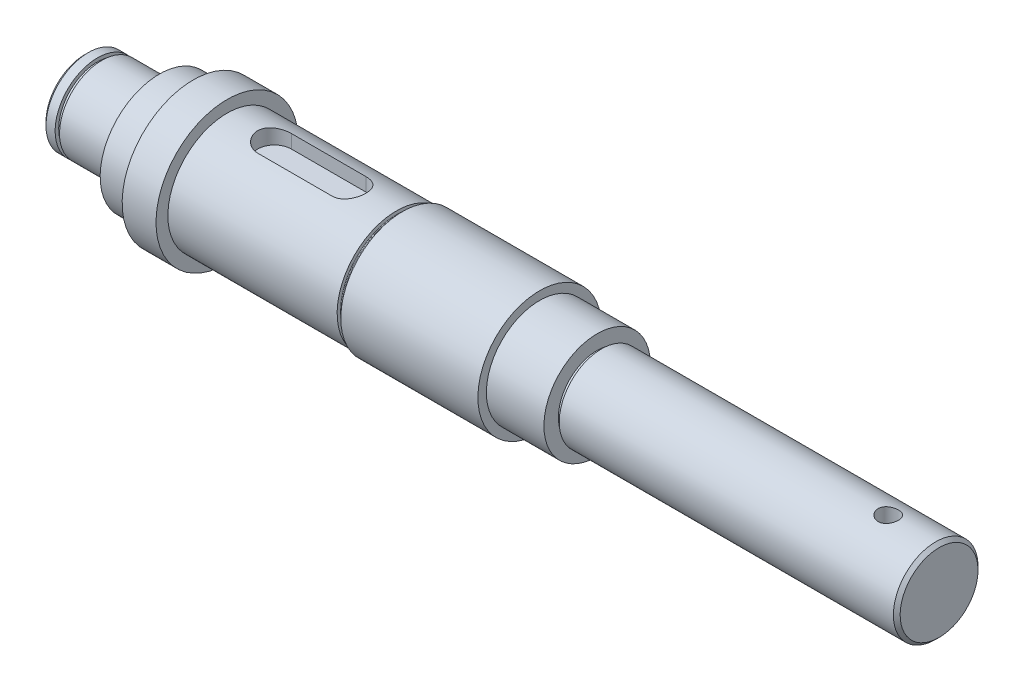
SolidWorks part; units mm, degrees
material "1023 Carbon Steel Sheet (SS)"
ref_plane "Front Plane" through (0, 0, 0) normal (0, 0, 1) x (1, 0, 0)
ref_plane "Top Plane" through (0, 0, 0) normal (0, 1, 0) x (1, 0, 0)
ref_plane "Right Plane" through (0, 0, 0) normal (1, 0, 0) x (0, 0, -1)
sketch "Sketch1" plane through (0, 0, 0) normal (0, 0, 1) x (1, 0, 0)
  line L0 (-4.1851, 0) -> (-4.1851, 11.5)
  line L1 (-3.1851, 12.5) -> (-0.4844, 12.5)
  line L2 (17.8149, 12.5) -> (17.8149, 17.5)
  line L3 (17.8149, 17.5) -> (27.8149, 17.5)
  line L4 (27.8149, 17.5) -> (27.8149, 21)
  line L5 (27.8149, 21) -> (37.8149, 21)
  line L6 (37.8149, 21) -> (37.8149, 17.5)
  line L7 (37.8149, 17.5) -> (87.8149, 17.5)
  line L8 (87.8149, 17.5) -> (87.9163, 16.6367)
  line L9 (88.1149, 16.46) -> (89.4149, 16.46)
  line L10 (89.6149, 17.3868) -> (89.6149, 18.2268)
  line L11 (89.6149, 18.2268) -> (130.1149, 18.2268)
  line L12 (130.1149, 18.2268) -> (130.1149, 15.7268)
  line L13 (130.1149, 15.7268) -> (147.1149, 15.7268)
  line L14 (-4.1851, 0) -> (248.1149, 0)
  line L15 (248.1149, 0) -> (248.1149, 11.5)
  line L16 (-15.3109, 0) -> (272.0087, 0) construction
  line L17 (147.1149, 15.7268) -> (147.1149, 11.45)
  line L18 (148.4149, 12.5) -> (247.1149, 12.5)
  line L19 (247.1149, 12.5) -> (248.1149, 11.5)
  line L20 (-4.1851, 11.5) -> (-3.1851, 12.5)
  line L21 (0.8156, 12.5) -> (0.8156, 11.45)
  line L22 (147.1149, 11.45) -> (148.4149, 11.45)
  line L23 (148.4149, 11.45) -> (148.4149, 12.5)
  line L24 (0.8156, 11.45) -> (-0.4844, 11.45)
  line L25 (-0.4844, 11.45) -> (-0.4844, 12.5)
  line L26 (0.8156, 12.5) -> (17.8149, 12.5)
  arc A0 (88.1149, 16.46) -> (87.9163, 16.6367) centre (88.1149, 16.66) cw
  arc A1 (89.4149, 16.46) -> (89.6149, 17.3868) centre (89.5149, 16.9234) ccw
  point P1 (-4.1851, 12.5)
  point P16 (248.1149, 12.5)
  dimension "D7" = 17
  dimension "D5" = 0.2
  dimension "D2" = 35
  dimension "D3" = 42
  dimension "D4" = 50
  dimension "D6" = 10
  dimension "D8" = 1.3
  dimension "D9" = 22
  dimension "D10" = 40.5
  dimension "D12" = 10
  dimension "D13" = 25
  dimension "D14" = 25
  dimension "D15" = 1.05
  dimension "D16" = 1.05
  dimension "D17" = 1.3
  dimension "D18" = 1.04
  dimension "D19" = 1.3
  dimension "D20" = 35
  dimension "D21" = 11.5
  dimension "D22" = 252.3
  dimension "D23" = 98.7
  dimension "D24" = 15.7268
revolve "Revolve1" add sketch "Sketch1" angle 360 about L16
sketch "Sketch3" plane through (0, 0, 0) normal (0, 1, 0) x (1, 0, 0)
  line L0 (51.8149, 0) -> (73.8149, 0) construction
  line L1 (51.8149, 5) -> (73.8149, 5)
  line L2 (51.8149, -5) -> (73.8149, -5)
  line L6 (37.8149, -17.5) -> (37.8149, 17.5) construction
  arc A0 (51.8149, 5) -> (51.8149, -5) centre (51.8149, 0) ccw
  arc A1 (73.8149, -5) -> (73.8149, 5) centre (73.8149, 0) ccw
  point P3 (62.8149, 0)
  point P8 (78.8149, 0)
  point P9 (46.8149, 0)
  dimension "D3" = 9
  dimension "D1" = 10
  dimension "D2" = 32
extrude "Cut-Extrude2" cut sketch "Sketch3" against normal blind 5.2 from offset 18
sketch "Sketch4" plane through (0, 0, 0) normal (0, 1, 0) x (1, 0, 0)
  line L0 (248.1149, -11.5) -> (248.1149, 11.5) construction
  circle A0 centre (233.1149, 0) radius 3
  dimension "D1" = 15
extrude "Cut-Extrude3" cut sketch "Sketch4" against normal mid plane 40
ref_axis "Axis1" through (254.9549, 0, 0) along (-1, 0, 0)
